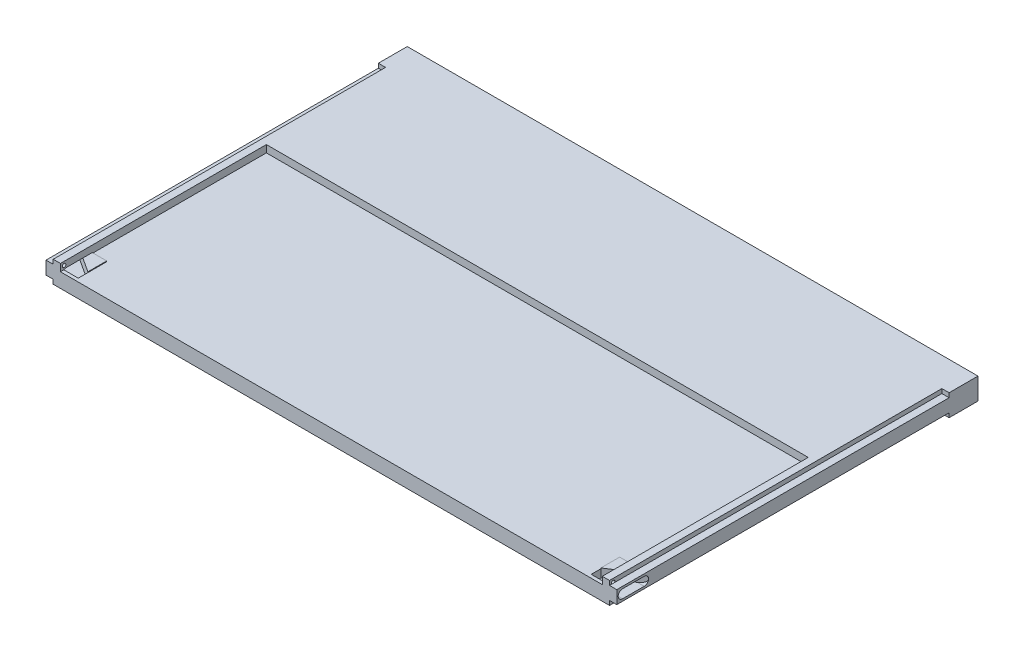
SolidWorks part; units mm, degrees
other "Markup1"
sketch "Sketch12" plane through (250.825, 22.225, 158.75) normal (0.1153, 0.0728, 0.9907) x (0.9687, -0.2289, -0.0959)
material "6061 Alloy"
ref_plane "Front Plane" through (0, 0, 0) normal (0, 0, 1) x (1, 0, 0)
ref_plane "Top Plane" through (0, 0, 0) normal (0, 1, 0) x (1, 0, 0)
ref_plane "Right Plane" through (0, 0, 0) normal (1, 0, 0) x (0, 0, -1)
sketch "Sketch1" plane through (0, 0, 0) normal (0, 1, 0) x (1, 0, 0)
  line L1 (-244.475, 158.75) -> (244.475, 158.75)
  line L2 (-244.475, 158.75) -> (-244.475, -158.75)
  line L3 (-244.475, -158.75) -> (244.475, -158.75)
  line L4 (244.475, 158.75) -> (244.475, -158.75)
  line L5 (-244.475, 158.75) -> (244.475, -158.75) construction
  line L6 (-244.475, -158.75) -> (244.475, 158.75) construction
  point P0 (0, 0)
  dimension "D1" = 488.95
  dimension "D2" = 317.5
extrude "Boss-Extrude1" add sketch "Sketch1" along normal blind 12.7
sketch "Sketch2" plane through (0, 12.7, 0) normal (0, 1, 0) x (1, 0, 0)
  line L0 (-244.475, -158.75) -> (244.475, -158.75) construction
  line L1 (-244.475, 158.75) -> (-238.125, 158.75)
  line L2 (-244.475, 158.75) -> (-244.475, -158.75)
  line L3 (-244.475, -158.75) -> (-238.125, -158.75)
  line L4 (-238.125, 22.225) -> (-238.125, -158.75)
  line L5 (244.475, 158.75) -> (-244.475, 158.75) construction
  line L6 (244.475, 158.75) -> (238.125, 158.75)
  line L7 (244.475, 158.75) -> (244.475, -158.75)
  line L8 (244.475, -158.75) -> (238.125, -158.75)
  line L9 (238.125, 22.225) -> (238.125, -158.75)
  line L10 (-238.125, 158.75) -> (238.125, 158.75)
  line L12 (-238.125, 22.225) -> (238.125, 22.225)
  point P14 (-241.3, -158.75)
  dimension "D1" = 6.35
  dimension "D2" = 180.975
extrude "Boss-Extrude2" add sketch "Sketch2" along normal blind 6.35
sketch "Sketch3" plane through (-244.475, 0, 0) normal (-1, 0, 0) x (0, 0, 1)
  line L0 (158.75, 19.05) -> (158.75, 0) construction
  line L1 (-158.75, 19.05) -> (158.75, 19.05) construction
  circle A0 centre (155.575, 15.875) radius 1.5875
  dimension "D3" = 3.175
  dimension "D1" = 3.175
  dimension "D2" = 3.175
extrude "Cut-Extrude1" cut sketch "Sketch3" against normal through all
sketch "Sketch4" plane through (0, 0, 158.75) normal (0, 0, 1) x (1, 0, 0)
  line L0 (-244.475, 19.05) -> (-244.475, 0) construction
  line L1 (-244.475, 15.24) -> (-250.825, 15.24)
  line L2 (-244.475, 15.24) -> (-244.475, 3.81)
  line L3 (-244.475, 3.81) -> (-250.825, 3.81)
  line L4 (-250.825, 15.24) -> (-250.825, 3.81)
  point P12 (-244.475, 9.525)
  dimension "D1" = 11.43
  dimension "D2" = 6.35
extrude "Boss-Extrude3" add sketch "Sketch4" against normal blind 292.1
sketch "Sketch5" plane through (-244.475, 0, 0) normal (-1, 0, 0) x (0, 0, 1)
  line L0 (-158.75, 0) -> (158.75, 0) construction
  line L1 (-158.75, 19.05) -> (-133.35, 19.05)
  line L2 (-158.75, 19.05) -> (-158.75, 0)
  line L3 (-158.75, 0) -> (-133.35, 0)
  line L4 (-133.35, 19.05) -> (-133.35, 0)
  line L5 (-133.35, 3.81) -> (-133.35, 15.24) construction
extrude "Boss-Extrude4" add sketch "Sketch5" along normal up to surface (6.35 mm away) up to face at (-250.825, 9.525, 12.7)
mirror "Mirror1" about plane through (0, 0, 0) normal (1, 0, 0) of "Boss-Extrude4", "Boss-Extrude3"
sketch "Sketch6" plane through (-244.475, 0, 0) normal (-1, 0, 0) x (0, 0, 1)
  line L0 (153.67, 9.525) -> (134.62, 9.525) construction
  line L1 (153.67, 5.715) -> (134.62, 5.715)
  line L2 (153.67, 13.335) -> (134.62, 13.335)
  line L3 (158.75, 3.81) -> (158.75, 0) construction
  line L5 (158.75, 15.24) -> (158.75, 3.81) construction
  arc A0 (153.67, 5.715) -> (153.67, 13.335) centre (153.67, 9.525) ccw
  arc A1 (134.62, 13.335) -> (134.62, 5.715) centre (134.62, 9.525) ccw
  point P2 (144.145, 9.525)
  point P11 (158.75, 9.525)
  dimension "D1" = 19.05
  dimension "D2" = 5.08
  dimension "D3" = 7.62
extrude "Cut-Extrude2" cut sketch "Sketch6" against normal blind 25.4 from surface starting at face at (-250.825, 9.525, -66.675)
extrude "Cut-Extrude3" cut sketch "Sketch6<2>" along normal blind 25.4 from surface starting at face at (250.825, 9.525, -66.675)
sketch "Sketch6<2>" plane through (-244.475, 0, 0) normal (-1, 0, 0) x (0, 0, 1) same geometry as "Sketch6"
sketch "Sketch11" plane through (0, 0, 0) normal (0, -1, 0) x (1, 0, 0)
  line L0 (-250.825, 130.81) -> (-225.425, 130.81)
  line L1 (-225.425, 130.81) -> (-225.425, 147.32)
  line L2 (-225.425, 147.32) -> (-250.825, 130.81)
  line L3 (-225.425, 134.62) -> (-225.425, 153.67) construction
  dimension "D1" = 10.16
extrude "Boss-Extrude5" add sketch "Sketch11" against normal up to surface (13.335 mm away) from surface up to face at (-244.475, 13.335, 144.145) starting at face at (-238.125, 5.715, 144.145)
mirror "Mirror2" about plane through (0, 0, 0) normal (1, 0, 0) of "Boss-Extrude5"
